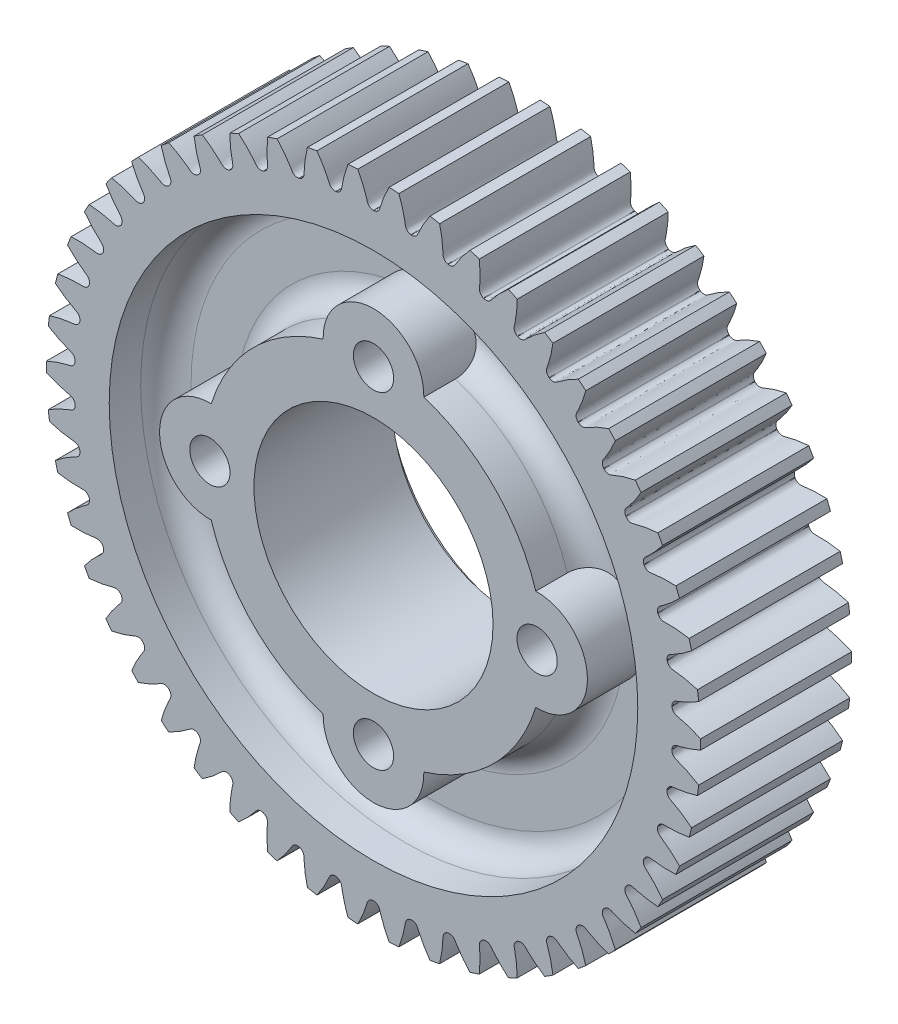
SolidWorks part; units mm, degrees
ref_plane "前视基准面" through (0, 0, 0) normal (0, 0, 1) x (1, 0, 0)
ref_plane "上视基准面" through (0, 0, 0) normal (0, 1, 0) x (1, 0, 0)
ref_plane "右视基准面" through (0, 0, 0) normal (1, 0, 0) x (0, 0, -1)
sketch "草图1" plane through (0, 0, 0) normal (0, 0, 1) x (1, 0, 0)
  circle A0 centre (0, 0) radius 26
extrude "凸台-拉伸1" add sketch "草图1" along normal blind 12
ref_axis "基准轴1" through (0, 0, 12) along (0, 0, -1)
sketch "草图2" plane through (0, 0, 0) normal (0, 0, 1) x (1, 0, 0)
  line L0 (0, 0) -> (0, 26) construction
  circle A0 centre (0, 0) radius 26 construction
  arc A1 (0.0183, 23.75) -> (-0.0183, 23.75) centre (0, 0) ccw
  arc A2 (3.8588, 29.4034) -> (-3.8588, 29.4034) centre (0, 0) ccw
  spline S0 degree 3 poles (0.0183, 23.75) (0.435, 23.8009) (0.4883, 24.1155) (0.5948, 24.4588) (0.6387, 24.5929) (0.6885, 24.735) (0.7445, 24.8848) (0.8068, 25.0423) (0.876, 25.2071) (0.9522, 25.3791) (1.0358, 25.5581) (1.1272, 25.7438) (1.2265, 25.9359) (1.3342, 26.1343) (1.4504, 26.3387) (1.5755, 26.5488) (1.7098, 26.7643) (1.8535, 26.985) (2.0068, 27.2105) (2.1701, 27.4406) (2.3435, 27.675) (2.5273, 27.9132) (2.7217, 28.1551) (2.9269, 28.4002) (3.1432, 28.6482) (3.4507, 28.9871) (3.6923, 29.2375) (3.8588, 29.4034) knots 0 0 0 0 0.116496 0.135538 0.155939 0.177697 0.200814 0.225289 0.251122 0.278313 0.306862 0.33677 0.368035 0.400659 0.434641 0.469981 0.506679 0.544736 0.584151 0.624923 0.667054 0.710544 0.755391 0.801596 0.84916 0.898082 1 1 1 1
  spline S1 degree 3 poles (-0.0183, 23.75) (-0.435, 23.8009) (-0.4883, 24.1155) (-0.5948, 24.4588) (-0.6387, 24.5929) (-0.6885, 24.735) (-0.7445, 24.8848) (-0.8068, 25.0423) (-0.876, 25.2071) (-0.9522, 25.3791) (-1.0358, 25.5581) (-1.1272, 25.7438) (-1.2265, 25.9359) (-1.3342, 26.1343) (-1.4504, 26.3387) (-1.5755, 26.5488) (-1.7098, 26.7643) (-1.8535, 26.985) (-2.0068, 27.2105) (-2.1701, 27.4406) (-2.3435, 27.675) (-2.5273, 27.9132) (-2.7217, 28.1551) (-2.9269, 28.4002) (-3.1432, 28.6482) (-3.4507, 28.9871) (-3.6923, 29.2375) (-3.8588, 29.4034) knots 0 0 0 0 0.116496 0.135538 0.155939 0.177697 0.200814 0.225289 0.251122 0.278313 0.306862 0.33677 0.368035 0.400659 0.434641 0.469981 0.506679 0.544736 0.584151 0.624923 0.667054 0.710544 0.755391 0.801596 0.84916 0.898082 1 1 1 1
extrude "切除-拉伸1" cut sketch "草图2" along normal through all
pattern_circular "阵列(圆周)1" count 50 every 7.2 about axis through (0, 0, 12) along (0, 0, -1) of "切除-拉伸1"
sketch "草图3" plane through (0, 0, 0) normal (0, 0, 1) x (1, 0, 0)
  circle A0 centre (0, 0) radius 25 construction
  dimension "Dn" = 50
sketch "草图4" plane through (0, 0, 12) normal (0, 0, 1) x (1, 0, 0)
  circle A0 centre (0, 0) radius 9.5
  dimension "D1" = 19
extrude "切除-拉伸2" cut sketch "草图4" against normal up to surface (12 mm away) up to face at (0, 0, 0)
sketch "草图5" plane through (0, 0, 12) normal (0, 0, 1) x (1, 0, 0)
  circle A0 centre (0, 0) radius 13 construction
  circle A1 centre (0, 13) radius 1.6
  dimension "D1" = 26
  dimension "D2" = 3.2
extrude "切除-拉伸3" cut sketch "草图5" against normal up to surface (12 mm away) up to face at (9.5, 0, 0)
pattern_circular "阵列(圆周)2" count 4 over 360 about axis through (0, 0, 12) along (0, 0, 1) of "切除-拉伸3"
sketch "草图6" plane through (0, 0, 0) normal (0, 0, -1) x (-1, 0, 0)
  circle A0 centre (0, 0) radius 10.75
  circle A1 centre (0, 0) radius 9.5 construction
  dimension "D1" = 21.5
extrude "切除-拉伸4" cut sketch "草图6" against normal blind 1
sketch "草图7" plane through (0, 0, 12) normal (0, 0, 1) x (1, 0, 0)
  arc A0 (-3.9986, 12.8942) -> (-12.8942, 3.9986) centre (0, 0) ccw
  circle A1 centre (0, 0) radius 9.5 construction
  arc A2 (-12.8942, 3.9986) -> (-12.8942, -3.9986) centre (-13, 0) ccw
  arc A3 (3.9986, 12.8942) -> (-3.9986, 12.8942) centre (0, 13) ccw
  arc A4 (12.8942, -3.9986) -> (12.8942, 3.9986) centre (13, 0) ccw
  arc A5 (-3.9986, -12.8942) -> (3.9986, -12.8942) centre (0, -13) ccw
  arc A6 (-12.8942, -3.9986) -> (-3.9986, -12.8942) centre (0, 0) ccw
  arc A7 (3.9986, -12.8942) -> (12.8942, -3.9986) centre (0, 0) ccw
  arc A8 (12.8942, 3.9986) -> (3.9986, 12.8942) centre (0, 0) ccw
  circle A9 centre (0, 0) radius 21
  arc A10 (-20.8043, 15.5943) -> (-21.2599, 14.9672) centre (0, 0) ccw construction
  dimension "D1" = 4
  dimension "D2" = 8
  dimension "D3" = 5
extrude "切除-拉伸5" cut sketch "草图7" against normal blind 4.5
ref_plane "基准面1" through (0, 0, 6) normal (0, 0, 1) x (1, 0, 0)
mirror "镜向1" about plane through (0, 0, 6) normal (0, 0, 1) of "切除-拉伸5"
fillet "圆角1" radius 2 10 edges at (9.5459, 9.5459, 7.5) (9.5459, -9.5459, 7.5) (-9.5459, -9.5459, 7.5) (21, 0, 7.5) (-9.5459, 9.5459, 7.5) (9.5459, 9.5459, 4.5) (-9.5459, 9.5459, 4.5) (-9.5459, -9.5459, 4.5) (9.5459, -9.5459, 4.5) (21, 0, 4.5)
